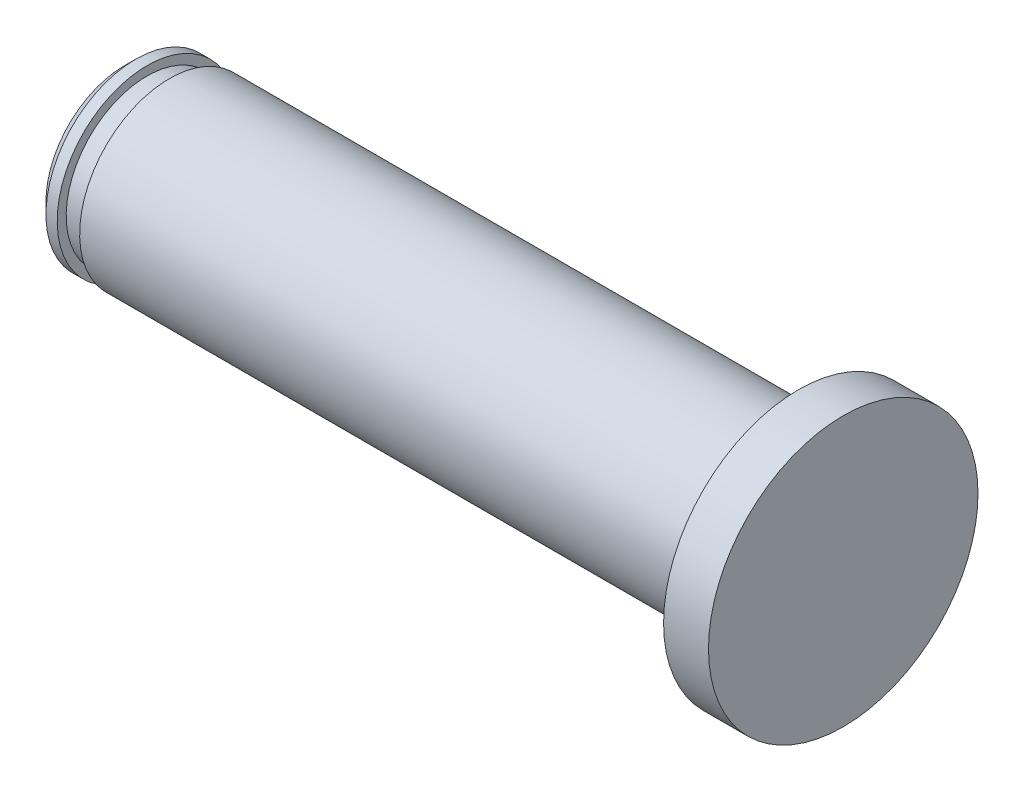
SolidWorks part; units mm, degrees
ref_plane "Спереди" through (0, 0, 0) normal (0, 0, 1) x (1, 0, 0)
ref_plane "Сверху" through (0, 0, 0) normal (0, 1, 0) x (1, 0, 0)
ref_plane "Справа" through (0, 0, 0) normal (1, 0, 0) x (0, 0, -1)
sketch "Эскиз1" plane through (0, 0, 0) normal (0, 0, 1) x (1, 0, 0)
  line L0 (0, 0) -> (-32, 0)
  line L1 (-32, 0) -> (-32, 4)
  line L2 (-32, 4) -> (-31, 4)
  line L3 (-31, 4) -> (-31, 3.6)
  line L4 (-31, 3.6) -> (-30, 3.6)
  line L5 (-30, 3.6) -> (-30, 4)
  line L6 (-30, 4) -> (-2, 4)
  line L7 (-2, 4) -> (-2, 6)
  line L8 (-2, 6) -> (0, 6)
  line L9 (0, 6) -> (0, 0)
  line L10 (-32, 0) -> (-24.8571, 0) construction
  line L11 (-32, 0) -> (-50032, 0) construction
  dimension "D1" = 8
  dimension "D2" = 28
  dimension "D3" = 2
  dimension "D4" = 2
  dimension "D5" = 1
  dimension "D6" = 1
  dimension "D7" = 7.2
revolve "Повернуть1" add sketch "Эскиз1" angle 360 about L10
chamfer "Фаска1" distance 0.5 angle 45 1 edges at (-32, -4, 0)
equation "\"Диаметр вала\" = 8  '!!!"
equation "\"Длина вала\" = 28"
equation "\"D1@Эскиз1\"=\"Диаметр вала\""
equation "\"D2@Эскиз1\"=\"Длина вала\""
